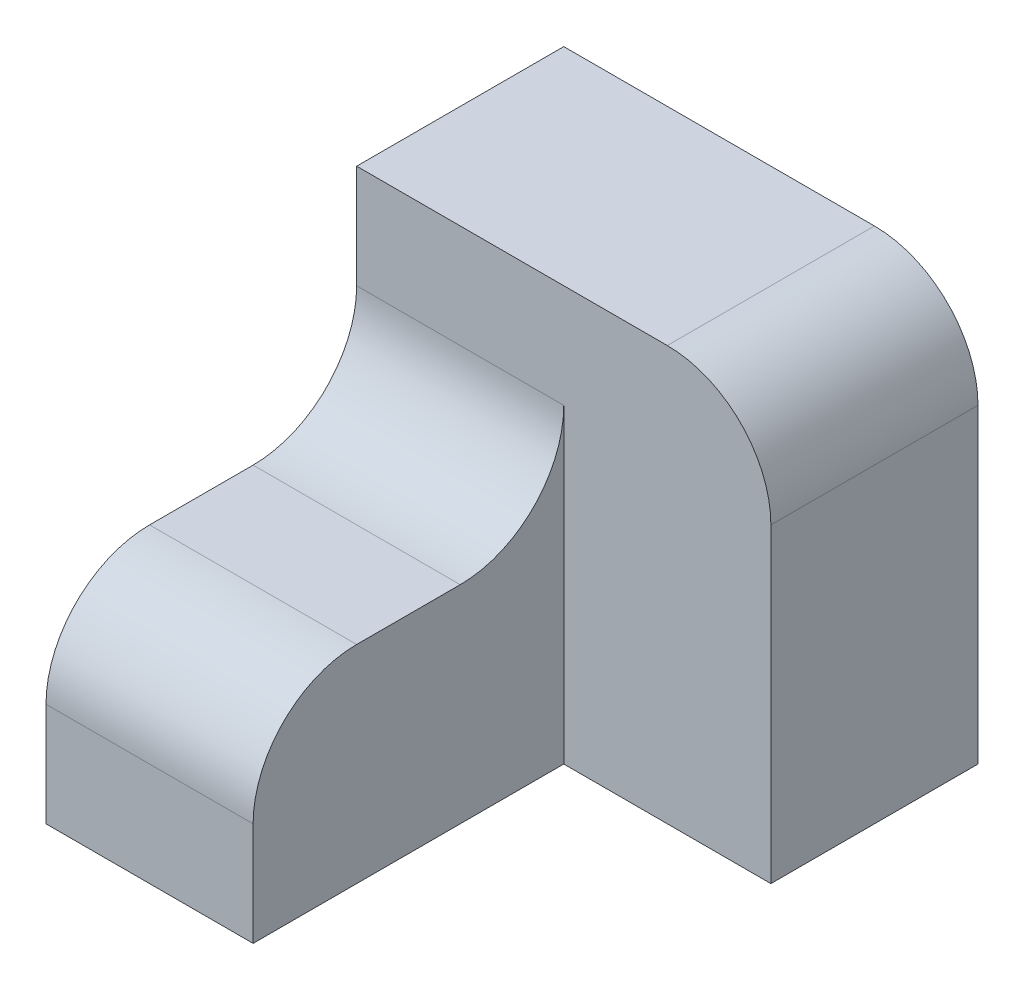
SolidWorks part; units mm, degrees
ref_plane "Front Plane" through (0, 0, 0) normal (0, 0, 1) x (1, 0, 0)
ref_plane "Top Plane" through (0, 0, 0) normal (0, 1, 0) x (1, 0, 0)
ref_plane "Right Plane" through (0, 0, 0) normal (1, 0, 0) x (0, 0, -1)
sketch "Sketch1" plane through (0, 0, 0) normal (0, 0, 1) x (1, 0, 0)
  line L1 (-30, -20) -> (-10, -20)
  line L2 (-10, -20) -> (-10, 0)
  line L3 (-10, 0) -> (-30, 0)
  line L4 (-30, 0) -> (-30, -20)
  dimension "D1" = 20
  dimension "Width" = 20
extrude "Boss-Extrude1" add sketch "Sketch1" along normal blind 30
sketch "Sketch2" plane through (0, 0, 0) normal (0, 0, 1) x (1, 0, 0)
  line L1 (-30, -20) -> (10, -20)
  line L2 (10, -20) -> (10, 20)
  line L3 (10, 20) -> (-30, 20)
  line L4 (-30, 20) -> (-30, -20)
  point P3 (-30, -20)
  dimension "D1" = 40
  dimension "Width" = 40
extrude "Boss-Extrude2" add sketch "Sketch2" against normal blind 20
fillet "Fillet1" radius 10 3 edges at (-20, 0, 0) (10, 20, -10) (-20, 0, 30)
